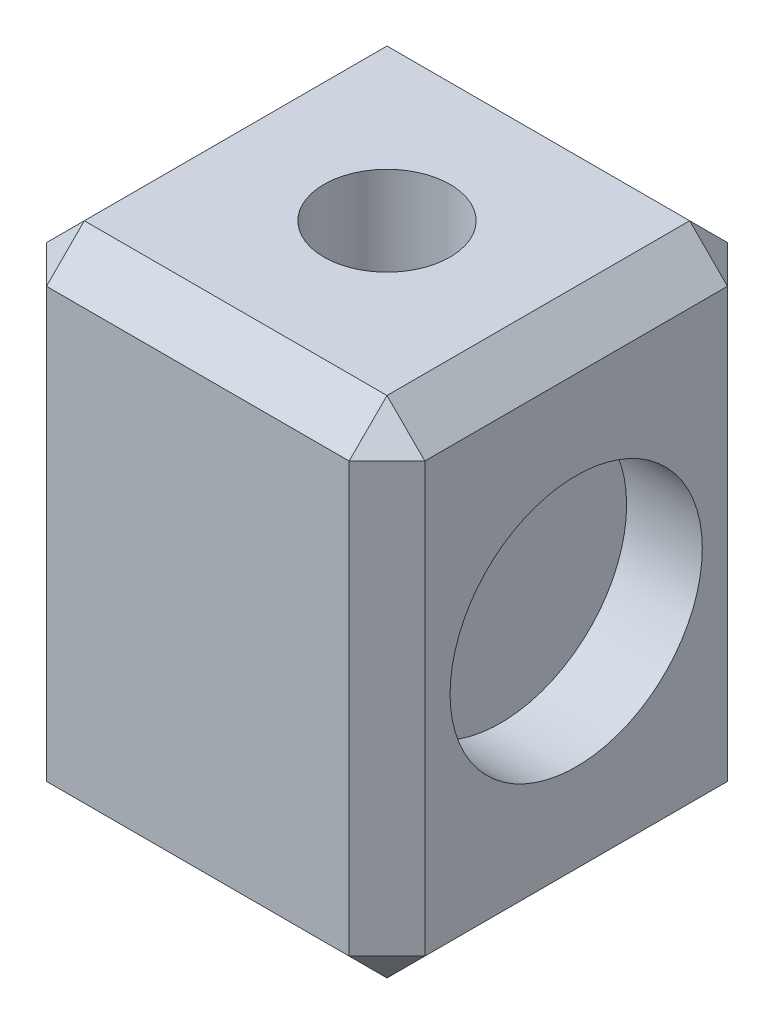
SolidWorks part; units mm, degrees
ref_plane "Front Plane" through (0, 0, 0) normal (0, 0, 1) x (1, 0, 0)
ref_plane "Top Plane" through (0, 0, 0) normal (0, 1, 0) x (1, 0, 0)
ref_plane "Right Plane" through (0, 0, 0) normal (1, 0, 0) x (0, 0, -1)
sketch "Sketch1" plane through (0, 0, 0) normal (0, 1, 0) x (1, 0, 0)
  line L1 (-19.05, -19.05) -> (19.05, -19.05)
  line L2 (-19.05, -19.05) -> (-19.05, 19.05)
  line L3 (-19.05, 19.05) -> (19.05, 19.05)
  line L4 (19.05, -19.05) -> (19.05, 19.05)
  line L5 (-19.05, -19.05) -> (19.05, 19.05) construction
  line L6 (-19.05, 19.05) -> (19.05, -19.05) construction
  circle A0 centre (0, 0) radius 6.35
  dimension "D1" = 12.7
  dimension "D2" = 38.1
  dimension "D3" = 38.1
extrude "Boss-Extrude1" add sketch "Sketch1" along normal blind 50.8
sketch "Sketch2" plane through (0, 0, 0) normal (1, 0, 0) x (0, 0, -1)
  line L0 (0, 50.8) -> (0, 0) construction
  line L1 (-19.05, 50.8) -> (19.05, 50.8) construction
  line L2 (-19.05, 25.4) -> (19.05, 25.4) construction
  line L3 (-19.05, 50.8) -> (-19.05, 0) construction
  line L4 (19.05, 50.8) -> (19.05, 0) construction
  circle A0 centre (0, 25.4) radius 12.7
  dimension "D1" = 25.4
extrude "Cut-Extrude1" cut sketch "Sketch2" against normal blind 7.62 from surface starting at face at (19.05, 25.4, 0)
extrude "Cut-Extrude2" cut sketch "Sketch2<2>" along normal blind 7.62 from surface starting at face at (-19.05, 25.4, 0)
sketch "Sketch2<2>" plane through (0, 0, 0) normal (1, 0, 0) x (0, 0, -1) same geometry as "Sketch2"
chamfer "Chamfer1" distance 3.81 angle 45 12 edges at (0, 0, 19.05) (-19.05, 0, 0) (19.05, 0, 0) (0, 0, -19.05) (-19.05, 25.4, -19.05) (-19.05, 25.4, 19.05) (-19.05, 50.8, 0) (0, 50.8, 19.05) (19.05, 25.4, 19.05) (19.05, 25.4, -19.05) (19.05, 50.8, 0) (0, 50.8, -19.05)
